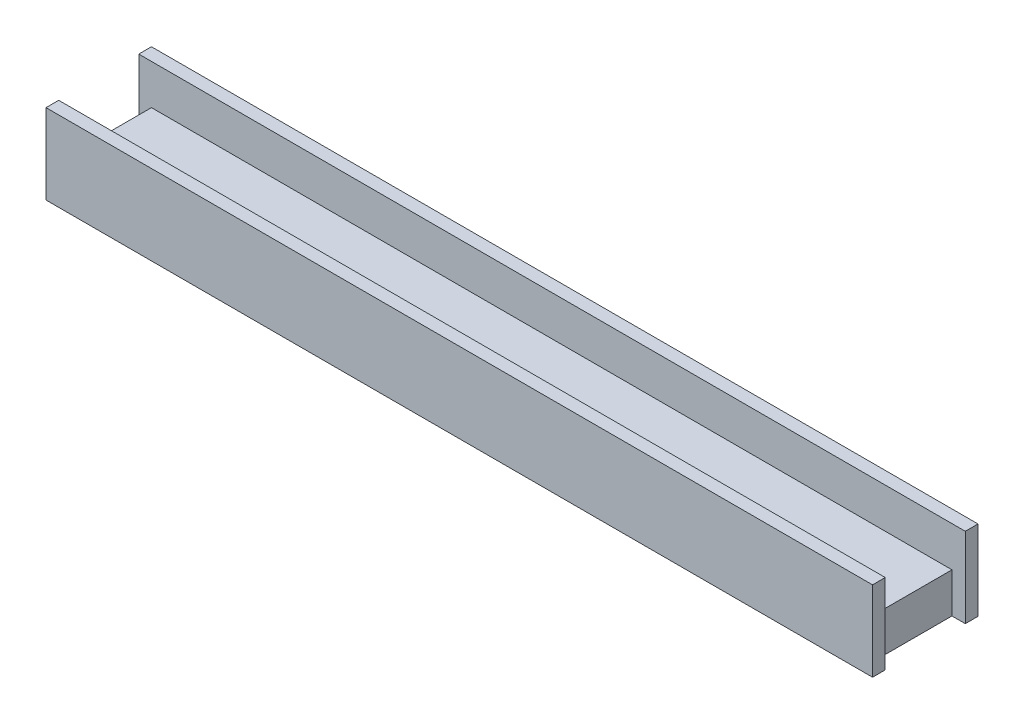
SolidWorks part; units mm, degrees
ref_plane "Front Plane" through (0, 0, 0) normal (0, 0, 1) x (1, 0, 0)
ref_plane "Top Plane" through (0, 0, 0) normal (0, 1, 0) x (1, 0, 0)
ref_plane "Right Plane" through (0, 0, 0) normal (1, 0, 0) x (0, 0, -1)
sketch "Sketch1" plane through (0, 0, 0) normal (0, 1, 0) x (1, 0, 0)
  line L0 (-0.7927, -5) -> (50.8328, -5)
  line L1 (0, 0) -> (50, 0)
  line L2 (0, 0) -> (0, -5)
  line L3 (0, -5) -> (50, -5)
  line L4 (50, 0) -> (50, -5)
  line L5 (-0.7927, 0.7937) -> (50.8328, 0.7937)
  line L6 (-0.7927, 0.7937) -> (-0.7927, 0)
  line L7 (-0.7927, 0) -> (50.8328, 0)
  line L8 (50.8328, 0.7937) -> (50.8328, 0)
  line L9 (50.8328, -5) -> (50.8328, -5.7937)
  line L10 (50.8328, -5.7937) -> (-0.7927, -5.7937)
  line L11 (-0.7927, -5.7937) -> (-0.7927, -5)
  dimension "D1" = 50
  dimension "D2" = 5
  dimension "D3" = 0.7937
  dimension "D4" = 0.7937
  dimension "D5" = 51.6255
extrude "Boss-Extrude1" add sketch "Sketch1" along normal blind 2.5 contours L4 L1 L2 L3 region at (25, 0, 2.5)
extrude "Boss-Extrude2" add sketch "Sketch1<3>" along normal blind 5 separate body contours L8 L5 L6 L7 L1 | L10 L11 L0 L9 region at (25.0201, 0, -0.3969)
sketch "Sketch1<3>" plane through (0, 0, 0) normal (0, 1, 0) x (1, 0, 0) same geometry as "Sketch1"
